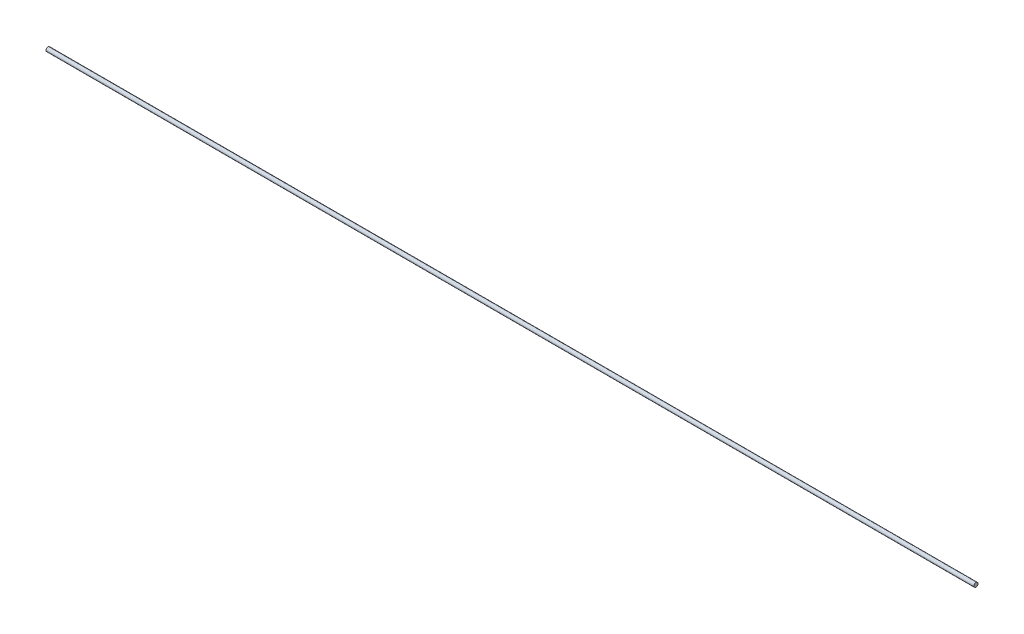
SolidWorks part; units mm, degrees
ref_plane "Front" through (0, 0, 0) normal (0, 0, 1) x (1, 0, 0)
ref_plane "Top" through (0, 0, 0) normal (0, 1, 0) x (1, 0, 0)
ref_plane "Right" through (0, 0, 0) normal (1, 0, 0) x (0, 0, -1)
sketch "Sketch1" plane through (0, 0, 0) normal (0, 0, 1) x (1, 0, 0)
  line L0 (0, 0) -> (34.3951, 0) construction
  line L1 (0, 0) -> (0, 3.175)
  line L2 (0, 3.175) -> (1441.3705, 3.175)
  line L3 (1441.3705, 3.175) -> (1441.3705, 0)
  line L4 (1441.3705, 0) -> (0, 0)
  line L5 (1441.3705, 3.25) -> (1441.3705, -3.25) construction
  dimension "D1" = 6.35
revolve "Revolve1" add sketch "Sketch1" angle 360 about L0
